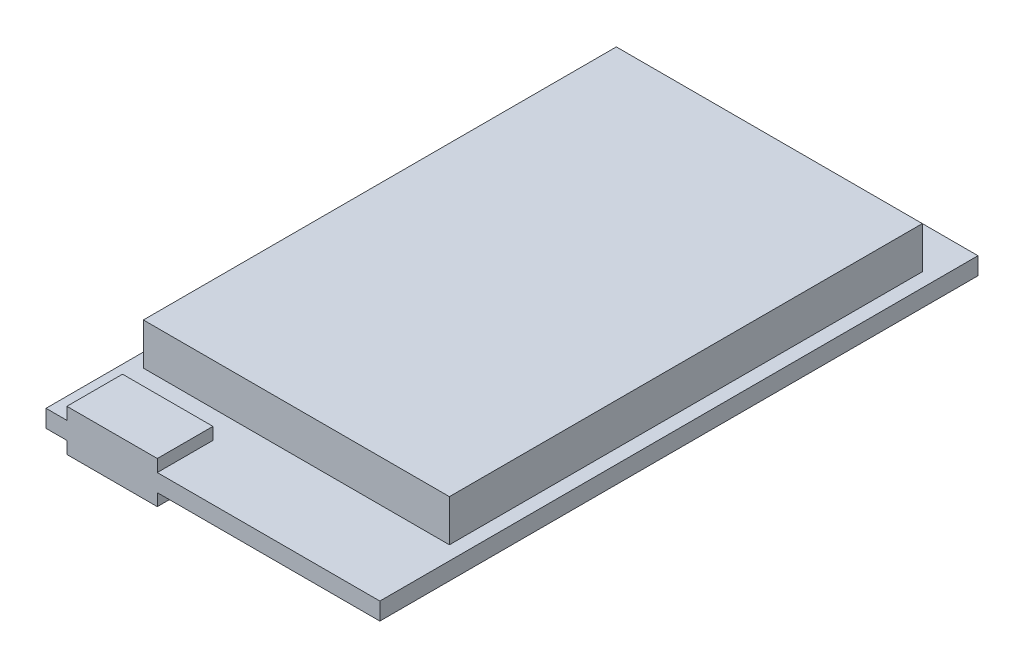
SolidWorks part; units mm, degrees
ref_plane "Front Plane" through (0, 0, 0) normal (0, 0, 1) x (1, 0, 0)
ref_plane "Top Plane" through (0, 0, 0) normal (0, 1, 0) x (1, 0, 0)
ref_plane "Right Plane" through (0, 0, 0) normal (1, 0, 0) x (0, 0, -1)
sketch "Sketch1" plane through (0, 0, 0) normal (0, 1, 0) x (1, 0, 0)
  line L1 (-12, 21.5) -> (12, 21.5)
  line L2 (-12, 21.5) -> (-12, -21.5)
  line L3 (-12, -21.5) -> (12, -21.5)
  line L4 (12, 21.5) -> (12, -21.5)
  line L5 (-12, 21.5) -> (12, -21.5) construction
  line L6 (-12, -21.5) -> (12, 21.5) construction
  point P0 (0, 0)
  dimension "D1" = 43
  dimension "D2" = 24
extrude "PCB" add sketch "Sketch1" along normal blind 1.25
sketch "Sketch2" plane through (0, 1.25, 0) normal (0, 1, 0) x (1, 0, 0)
  line L0 (-12, -21.5) -> (12, -21.5) construction
  line L1 (-11, 18.5) -> (11, 18.5)
  line L2 (-11, 18.5) -> (-11, -15.5)
  line L3 (-11, -15.5) -> (11, -15.5)
  line L4 (11, 18.5) -> (11, -15.5)
  line L5 (-11, 18.5) -> (11, -15.5) construction
  line L6 (-11, -15.5) -> (11, 18.5) construction
  point P0 (0, 1.5)
  dimension "D1" = 34
  dimension "D2" = 22
  dimension "D3" = 6
extrude "RF Casing" add sketch "Sketch2" along normal blind 3
sketch "Sketch5" plane through (0, 0, 21.5) normal (0, 0, 1) x (1, 0, 0)
  line L1 (-10.4992, 2.125) -> (-3.9992, 2.125)
  line L2 (-10.4992, 2.125) -> (-10.4992, -0.875)
  line L3 (-10.4992, -0.875) -> (-3.9992, -0.875)
  line L4 (-3.9992, 2.125) -> (-3.9992, -0.875)
  line L5 (-10.4992, 2.125) -> (-3.9992, -0.875) construction
  line L6 (-10.4992, -0.875) -> (-3.9992, 2.125) construction
  line L8 (-12, 1.25) -> (-12, 0) construction
  line L9 (-12, 1.25) -> (-12, 0) construction
  point P0 (-7.2492, 0.625)
  point P12 (-12, 0.625)
  dimension "D1" = 3
  dimension "D2" = 6.5
  dimension "D3" = 8.0008
extrude "Pins" add sketch "Sketch5" against normal blind 4
